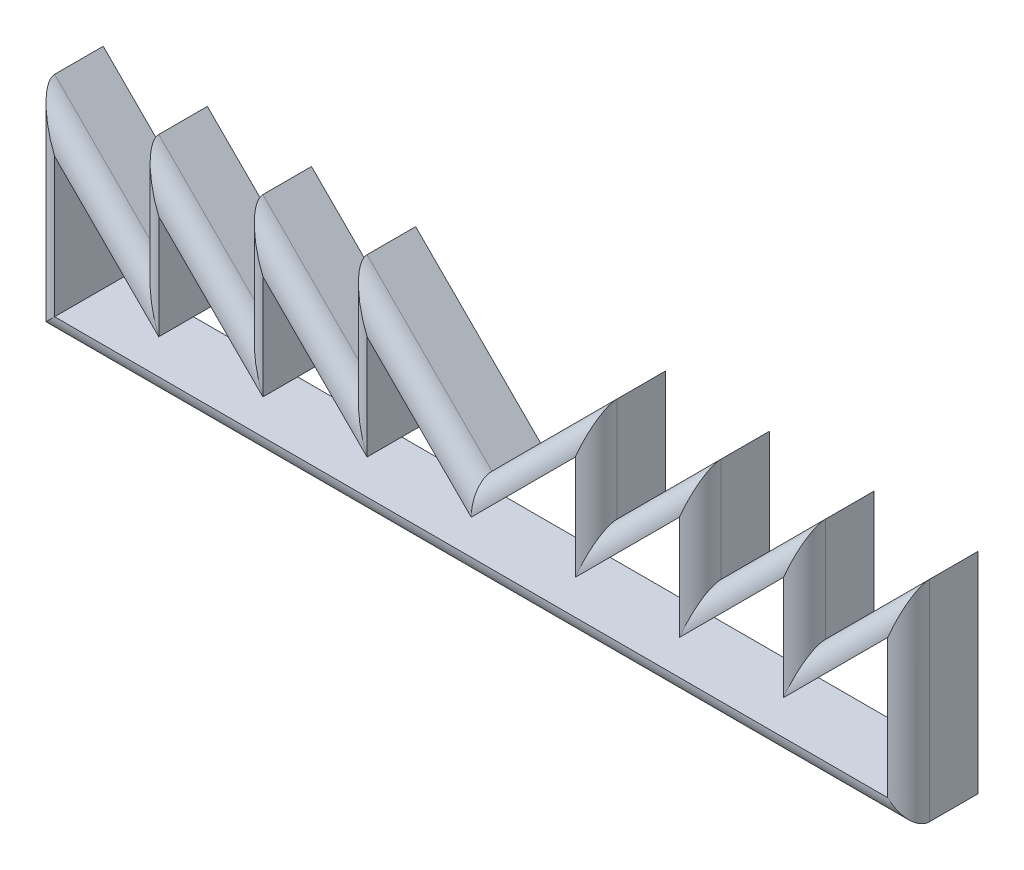
SolidWorks part; units mm, degrees
ref_plane "Front Plane" through (0, 0, 0) normal (0, 0, 1) x (1, 0, 0)
ref_plane "Top Plane" through (0, 0, 0) normal (0, 1, 0) x (1, 0, 0)
ref_plane "Right Plane" through (0, 0, 0) normal (1, 0, 0) x (0, 0, -1)
sketch "Sketch1" plane through (0, 0, 0) normal (0, 0, 1) x (1, 0, 0)
  line L0 (-60, 15) -> (-45, 0)
  line L1 (-45, 0) -> (-45, 15)
  line L2 (-45, 15) -> (-30, 0)
  line L3 (-30, 0) -> (-30, 15)
  line L4 (-30, 15) -> (-15, 0)
  line L5 (-15, 0) -> (-15, 15)
  line L6 (-15, 15) -> (0, 0)
  line L7 (0, 0) -> (15, 15)
  line L8 (15, 15) -> (15, 0)
  line L9 (15, 0) -> (30, 15)
  line L10 (30, 15) -> (30, 0)
  line L11 (30, 0) -> (45, 15)
  line L12 (45, 15) -> (45, 0)
  line L13 (45, 0) -> (60, 15)
  line L14 (60, 15) -> (60, -5)
  line L15 (60, -5) -> (-60, -5)
  line L16 (-60, -5) -> (-60, 15)
  line L17 (-33, 7.2426) -> (-33, 22.2426)
  line L18 (48, 7.2426) -> (63, 22.2426)
  line L19 (63, 22.2426) -> (63, -8)
  line L20 (-63, 22.2426) -> (-48, 7.2426)
  line L21 (18, 7.2426) -> (33, 22.2426)
  line L22 (48, 22.2426) -> (48, 7.2426)
  line L23 (63, -8) -> (-63, -8)
  line L24 (-33, 22.2426) -> (-18, 7.2426)
  line L25 (-18, 22.2426) -> (0, 4.2426)
  line L26 (-63, -8) -> (-63, 22.2426)
  line L27 (-48, 7.2426) -> (-48, 22.2426)
  line L28 (18, 22.2426) -> (18, 7.2426)
  line L29 (33, 7.2426) -> (48, 22.2426)
  line L30 (33, 22.2426) -> (33, 7.2426)
  line L31 (-18, 7.2426) -> (-18, 22.2426)
  line L32 (0, 4.2426) -> (18, 22.2426)
  line L33 (-48, 22.2426) -> (-33, 7.2426)
  dimension "D1" = 45
  dimension "D2" = 15
  dimension "D3" = 5
  dimension "D4" = 3
  dimension "D5" = 3
  dimension "D6" = 3
  dimension "D7" = 3
sketch "Sketch2" plane through (0, 0, 0) normal (0, 0, 1) x (1, 0, 0)
  line L0 (-60, 5) -> (-45, 20)
  line L1 (-45, 20) -> (-45, 5)
  line L2 (-45, 5) -> (-30, 20)
  line L3 (-30, 20) -> (-30, 5)
  line L4 (-30, 5) -> (-15, 20)
  line L5 (-15, 20) -> (-15, 5)
  line L6 (-15, 5) -> (0, 20)
  line L7 (0, 20) -> (0, 0)
  line L8 (-60, 52.2197) -> (-60, -17.7657) construction
  line L9 (0, 0) -> (-120, 0)
  line L10 (-120, 20) -> (-120, 0)
  line L11 (-105, 5) -> (-120, 20)
  line L12 (-105, 20) -> (-105, 5)
  line L13 (-90, 5) -> (-105, 20)
  line L14 (-90, 20) -> (-90, 5)
  line L15 (-75, 5) -> (-90, 20)
  line L16 (-75, 20) -> (-75, 5)
  line L17 (-60, 5) -> (-75, 20)
  line L18 (-60, 9.2426) -> (-42, 27.2426)
  line L19 (-42, 27.2426) -> (-42, 12.2426)
  line L20 (-42, 12.2426) -> (-27, 27.2426)
  line L21 (-27, 27.2426) -> (-27, 12.2426)
  line L22 (-27, 12.2426) -> (-12, 27.2426)
  line L23 (-12, 27.2426) -> (-12, 12.2426)
  line L24 (-12, 12.2426) -> (3, 27.2426)
  line L25 (3, 27.2426) -> (3, -3)
  line L26 (3, -3) -> (-123, -3)
  line L27 (-123, 27.2426) -> (-123, -3)
  line L28 (-108, 12.2426) -> (-123, 27.2426)
  line L29 (-108, 27.2426) -> (-108, 12.2426)
  line L30 (-93, 12.2426) -> (-108, 27.2426)
  line L31 (-93, 27.2426) -> (-93, 12.2426)
  line L32 (-78, 12.2426) -> (-93, 27.2426)
  line L33 (-78, 27.2426) -> (-78, 12.2426)
  line L34 (-60, 9.2426) -> (-78, 27.2426)
  point P14 (-60, 0)
  dimension "D1" = 45
  dimension "D3" = 5
  dimension "D4" = 15
  dimension "D5" = 3
  dimension "D2" = 4
extrude "Boss-Extrude1" add sketch "Sketch2" along normal blind 10
fillet "Fillet11" radius 3 17 edges at (-69, 18.2426, 10) (-51, 18.2426, 10) (-42, 19.7426, 10) (-34.5, 19.7426, 10) (-27, 19.7426, 10) (-19.5, 19.7426, 10) (-12, 19.7426, 10) (-4.5, 19.7426, 10) (3, 12.1213, 10) (-60, -3, 10) (-123, 12.1213, 10) (-115.5, 19.7426, 10) (-108, 19.7426, 10) (-100.5, 19.7426, 10) (-93, 19.7426, 10) (-85.5, 19.7426, 10) (-78, 19.7426, 10)
